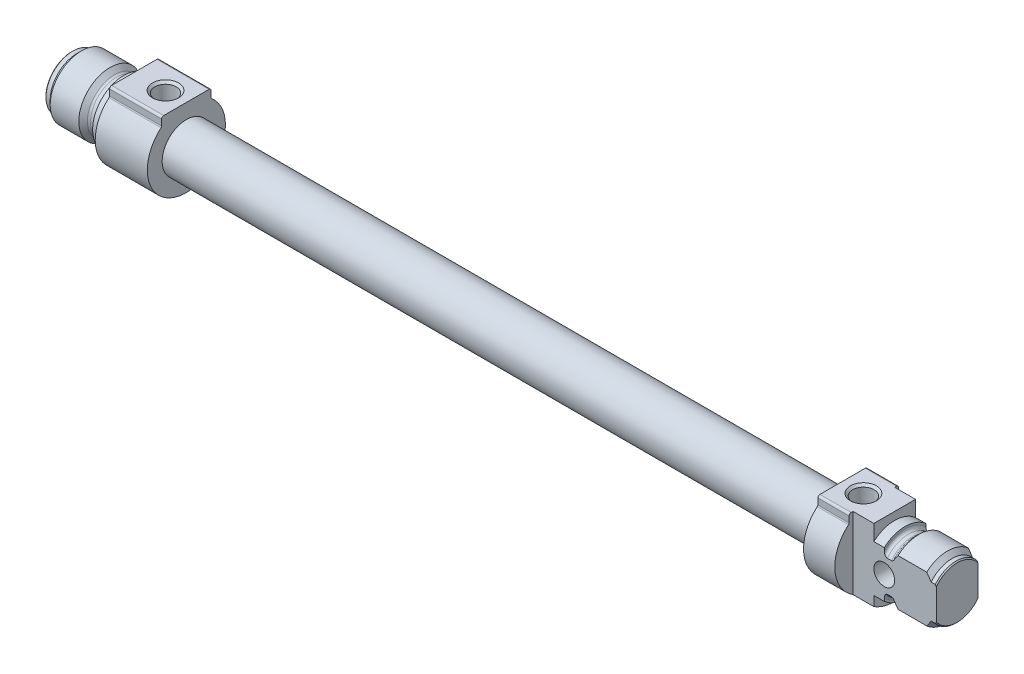
SolidWorks part; units mm, degrees
ref_plane "Ebene vorne" through (0, 0, 0) normal (0, 0, 1) x (1, 0, 0)
ref_plane "Ebene oben" through (0, 0, 0) normal (0, 1, 0) x (1, 0, 0)
ref_plane "Ebene rechts" through (0, 0, 0) normal (1, 0, 0) x (0, 0, -1)
sketch "Skizze1" plane through (0, 0, 0) normal (0, 0, 1) x (1, 0, 0)
  line L0 (0, 0) -> (0, 4.95)
  line L1 (0, 4.95) -> (0.2, 5.15)
  line L2 (0.2, 5.15) -> (1, 5.15)
  line L3 (1, 5.15) -> (1.85, 6)
  line L4 (1.85, 6) -> (7.35, 6)
  line L5 (7.35, 6) -> (8.1743, 5.1757)
  line L6 (8.5985, 5) -> (9.4, 5)
  line L7 (10, 5.6) -> (10, 6)
  line L8 (10, 6) -> (12, 6)
  line L9 (12, 6) -> (12, 0)
  line L10 (12, 0) -> (0, 0)
  line L11 (12, 0) -> (0, 0) construction
  arc A0 (8.1743, 5.1757) -> (8.5985, 5) centre (8.5985, 5.6) ccw
  arc A1 (9.4, 5) -> (10, 5.6) centre (9.4, 5.6) ccw
revolve "Rotation1" add sketch "Skizze1" angle 360 about L11 reverse direction yes
cosmetic thread "Gewindedarstellung1" parameters "D1"=6.267, "D2"=10.466
ref_plane "Ebene1" through (3, 0, 0) normal (1, 0, 0) x (0, 0, -1)
ref_plane "Ebene2" through (8, 0, 0) normal (1, 0, 0) x (0, 0, -1)
ref_plane "Ebene3" through (0, -8, 0) normal (0, 1, 0) x (1, 0, 0)
ref_plane "Ebene4" through (0, 0, 0) normal (0, 1, 0) x (1, 0, 0)
ref_plane "Ebene5" through (0, 0, 0) normal (0, 1, 0) x (1, 0, 0)
ref_plane "Ebene6" through (0, 0, 0) normal (0, 1, 0) x (1, 0, 0)
ref_plane "Ebene7" through (12, 0, 0) normal (1, 0, 0) x (0, 0, -1)
ref_plane "Ebene8" through (12, 0, 0) normal (1, 0, 0) x (0, 0, -1)
ref_plane "Ebene9" through (20, 0, 0) normal (1, 0, 0) x (0, 0, -1)
ref_plane "Ebene10" through (12, 0, 0) normal (1, 0, 0) x (0, 0, -1)
ref_plane "Ebene11" through (12, 0, 0) normal (1, 0, 0) x (0, 0, -1)
sketch "Skizze2" plane through (12, 0, 0) normal (1, 0, 0) x (0, 0, -1)
  line L0 (4.75, 5.9445) -> (4.75, 7.1)
  line L1 (4.35, 7.5) -> (-4.35, 7.5)
  line L2 (-4.75, 7.1) -> (-4.75, 5.9445)
  arc A0 (-4.8558, 5.7159) -> (4.8558, 5.7159) centre (0, 0) ccw
  arc A1 (4.8558, 5.7159) -> (4.75, 5.9445) centre (5.05, 5.9445) cw
  arc A2 (4.75, 7.1) -> (4.35, 7.5) centre (4.35, 7.1) ccw
  arc A3 (-4.35, 7.5) -> (-4.75, 7.1) centre (-4.35, 7.1) ccw
  arc A4 (-4.75, 5.9445) -> (-4.8558, 5.7159) centre (-5.05, 5.9445) cw
extrude "Aufsatz-Linear austragen1" add sketch "Skizze2" along normal blind 10
ref_plane "Ebene12" through (12, 0, 0) normal (1, 0, 0) x (0, 0, -1)
ref_plane "Ebene13" through (0, 0, 0) normal (0, 0, 1) x (1, 0, 0)
ref_plane "Ebene14" through (0, 0, 0) normal (0, 0, 1) x (1, 0, 0)
ref_plane "Ebene15" through (0, 0, 0) normal (0, 1, 0) x (1, 0, 0)
ref_plane "Ebene16" through (0, 0, 0) normal (0, 1, 0) x (1, 0, 0)
ref_plane "Ebene17" through (0, 0, -6.6) normal (0, 0, 1) x (1, 0, 0)
ref_plane "Ebene18" through (0, 0, 0) normal (0, 1, 0) x (1, 0, 0)
ref_plane "Ebene19" through (0, 0, 0) normal (0, 1, 0) x (1, 0, 0)
ref_plane "Ebene20" through (0, 1.1287, -0.199) normal (0, 0.9848, -0.1736) x (1, 0, 0)
ref_plane "Ebene21" through (0, -0.3485, 0.0615) normal (0, 0.9848, -0.1736) x (1, 0, 0)
sketch "Skizze3" plane through (0, 0, 0) normal (0, 0, 1) x (1, 0, 0)
  line L0 (22, 0) -> (22, 4.65)
  line L1 (22, 4.65) -> (148, 4.65)
  line L2 (148, 4.65) -> (148, 0)
  line L3 (148, 0) -> (22, 0)
  line L4 (148, 0) -> (22, 0) construction
revolve "Rotation2" add sketch "Skizze3" angle 360 about L4 reverse direction yes
ref_plane "Ebene22" through (148, 0, 0) normal (1, 0, 0) x (0, 0, -1)
sketch "Skizze4" plane through (148, 0, 0) normal (1, 0, 0) x (0, 0, -1)
  line L0 (4.75, 5.9445) -> (4.75, 7.1)
  line L1 (4.35, 7.5) -> (-4.35, 7.5)
  line L2 (-4.75, 7.1) -> (-4.75, 5.9445)
  arc A0 (-4.8558, 5.7159) -> (4.8558, 5.7159) centre (0, 0) ccw
  arc A1 (4.8558, 5.7159) -> (4.75, 5.9445) centre (5.05, 5.9445) cw
  arc A2 (4.75, 7.1) -> (4.35, 7.5) centre (4.35, 7.1) ccw
  arc A3 (-4.35, 7.5) -> (-4.75, 7.1) centre (-4.35, 7.1) ccw
  arc A4 (-4.75, 5.9445) -> (-4.8558, 5.7159) centre (-5.05, 5.9445) cw
extrude "Aufsatz-Linear austragen2" add sketch "Skizze4" along normal blind 10
ref_plane "Ebene23" through (148, 0, 0) normal (1, 0, 0) x (0, 0, -1)
ref_plane "Ebene24" through (158, 0, 0) normal (1, 0, 0) x (0, 0, -1)
ref_plane "Ebene25" through (0, 0, 6.6) normal (0, 0, 1) x (1, 0, 0)
ref_plane "Ebene26" through (0, 0, 0) normal (0, 1, 0) x (1, 0, 0)
ref_plane "Ebene27" through (0, 0, 0) normal (0, 1, 0) x (1, 0, 0)
ref_plane "Ebene28" through (0, 1.1287, 0.199) normal (0, 0.9848, 0.1736) x (1, 0, 0)
ref_plane "Ebene29" through (0, -0.3485, -0.0615) normal (0, 0.9848, 0.1736) x (1, 0, 0)
ref_plane "Ebene30" through (187, 0, 0) normal (1, 0, 0) x (0, 0, -1)
sketch "Skizze5" plane through (0, 0, 0) normal (0, 0, 1) x (1, 0, 0)
  line L0 (158, 0) -> (158, 6)
  line L1 (158, 6) -> (160, 6)
  line L2 (160, 6) -> (160, 5.6)
  line L3 (160.6, 5) -> (161.4015, 5)
  line L4 (161.8257, 5.1757) -> (162.65, 6)
  line L5 (162.65, 6) -> (168.15, 6)
  line L6 (168.15, 6) -> (169, 5.15)
  line L7 (169, 5.15) -> (169.8, 5.15)
  line L8 (169.8, 5.15) -> (170, 4.95)
  line L9 (170, 4.95) -> (170, 0)
  line L10 (170, 0) -> (158, 0)
  line L11 (170, 0) -> (158, 0) construction
  arc A0 (160, 5.6) -> (160.6, 5) centre (160.6, 5.6) ccw
  arc A1 (161.4015, 5) -> (161.8257, 5.1757) centre (161.4015, 5.6) ccw
revolve "Rotation3" add sketch "Skizze5" angle 360 about L11 reverse direction yes
cosmetic thread "Gewindedarstellung2" parameters "D1"=5.417, "D2"=10.466
ref_plane "Ebene31" through (179, 0, 0) normal (1, 0, 0) x (0, 0, -1)
ref_plane "Ebene32" through (187, 0, 0) normal (1, 0, 0) x (0, 0, -1)
ref_plane "Ebene33" through (187, 0, 0) normal (1, 0, 0) x (0, 0, -1)
sketch "Skizze6" plane through (0, 0, 0) normal (0, 1, 0) x (1, 0, 0)
  line L0 (154, 12) -> (154, 4)
  line L1 (154, 4) -> (170, 4)
  line L2 (170, 4) -> (170, -4)
  line L3 (170, -4) -> (154, -4)
  line L4 (154, -4) -> (154, -12)
  line L5 (154, -12) -> (178, -12)
  line L6 (178, -12) -> (178, 12)
  line L7 (178, 12) -> (154, 12)
extrude "Schnitt-Linear austragen1" cut sketch "Skizze6" along normal blind 7.5 and the other way blind 7.5
ref_plane "Ebene34" through (160, 0, 0) normal (1, 0, 0) x (0, 0, -1)
hole_wizard "Bohrung1" positions "Skizze8" profile "Skizze7" legacy
sketch "Skizze8" plane through (0, 0, -4) normal (0, 0, -1) x (-1, 0, 0)
  point P0 (-160, 0)
sketch "Skizze7" plane through (160, 0, -4) normal (1, 0, 0) x (0, 1, 0)
  line L0 (0, 0) -> (0, 8)
  line L1 (0, 8) -> (2, 8)
  line L2 (2, 8) -> (2, 0)
  line L3 (2, 0) -> (0, 0)
  line L4 (0, 110) -> (0, -10) construction
  dimension "Durchmesser" = 4
  dimension "Tiefe" = 8
hole_wizard "Bohrung2" positions "Skizze10" profile "Skizze9" legacy
sketch "Skizze10" plane through (0, 7.5, 0) normal (0, 1, 0) x (1, 0, 0)
  point P0 (18, 0)
sketch "Skizze9" plane through (18, 7.5, 0) normal (1, 0, 0) x (0, 0, 1)
  line L0 (0, 0) -> (0, 7.5)
  line L1 (0, 7.5) -> (2.067, 7.5)
  line L2 (2.067, 7.5) -> (2.067, 0.433)
  line L3 (2.067, 0.433) -> (2.5, 0)
  line L4 (2.5, 0) -> (0, 0)
  line L5 (0, -6.4453) -> (0, 115.525) construction
  line L6 (-2.067, 0.433) -> (-2.5, 0) construction
  dimension "Durchmesser" = 4.134
  dimension "Tiefe" = 7.5
  dimension "Senkwinkel1" = 90
  dimension "Senkdurchmesser3" = 5
cosmetic thread "Gewindedarstellung3" parameters "D1"=5.5, "D2"=5
hole_wizard "Bohrung3" positions "Skizze12" profile "Skizze11" legacy
sketch "Skizze12" plane through (0, 7.5, 0) normal (0, 1, 0) x (1, 0, 0)
  point P0 (152, 0)
sketch "Skizze11" plane through (152, 7.5, 0) normal (1, 0, 0) x (0, 0, 1)
  line L0 (0, 0) -> (0, 9.1934)
  line L1 (0, 9.1934) -> (2.067, 8)
  line L2 (2.067, 8) -> (2.067, 0.433)
  line L3 (2.067, 0.433) -> (2.5, 0)
  line L4 (2.5, 0) -> (0, 0)
  line L5 (0, -14.3089) -> (0, 102.4216) construction
  line L6 (0, 9.1934) -> (-2.067, 8) construction
  line L7 (-2.067, 0.433) -> (-2.5, 0) construction
  dimension "Durchmesser" = 4.134
  dimension "Tiefe" = 8
  dimension "Senkdurchmesser1" = 5
  dimension "Senkwinkel1" = 90
  dimension "Spitzenwinkel" = 120
cosmetic thread "Gewindedarstellung4" parameters "D1"=6, "D2"=5
sketch "Skizze13" plane through (0, 0, 0) normal (0, 0, 1) x (1, 0, 0)
  line L0 (-4, 0) -> (-4, 2)
  line L1 (-4, 2) -> (31.5, 2)
  line L2 (31.5, 2) -> (31.5, 4)
  line L3 (31.5, 4) -> (133.5, 4)
  line L4 (133.5, 4) -> (133.5, 0)
  line L5 (133.5, 0) -> (-4, 0)
  line L6 (133.5, 0) -> (-4, 0) construction
revolve "Schnitt-Rotation1" cut sketch "Skizze13" angle 360 about L6 reverse direction yes
ref_plane "Ebene35" through (-4, 0, 0) normal (1, 0, 0) x (0, 0, -1)
ref_plane "Ebene36" through (0, 7.5, 0) normal (0, 1, 0) x (1, 0, 0)
ref_plane "Ebene37" through (8, 0, 0) normal (1, 0, 0) x (0, 0, -1)
ref_plane "Ebene38" through (0, 0, 0) normal (1, 0, 0) x (0, 0, -1)
ref_plane "Ebene39" through (12, 0, 0) normal (1, 0, 0) x (0, 0, -1)
ref_plane "Ebene40" through (158, 0, 0) normal (1, 0, 0) x (0, 0, -1)
ref_plane "Ebene41" through (12, 0, 0) normal (1, 0, 0) x (0, 0, -1)
ref_plane "Ebene42" through (0, 7.5, 0) normal (0, 1, 0) x (1, 0, 0)
ref_plane "Ebene43" through (31.5, 0, 0) normal (1, 0, 0) x (0, 0, -1)
ref_plane "Ebene44" through (138.5, 0, 0) normal (1, 0, 0) x (0, 0, -1)
ref_plane "Ebene45" through (0, 0, 0) normal (0, 0, 1) x (1, 0, 0)
ref_plane "Ebene46" through (12, 0, 0) normal (1, 0, 0) x (0, 0, -1)
ref_plane "Ebene47" through (0, 7.5, 0) normal (0, 1, 0) x (1, 0, 0)
ref_plane "FDT_FRONT XY" through (12, 0, 0) normal (1, 0, 0) x (0, 0, -1)
ref_plane "FDT_FRONT XZ" through (0, 0, 0) normal (0, -1, 0) x (-1, 0, 0)
ref_plane "FDT_FRONT YZ" through (0, 0, 0) normal (0, 0, -1) x (-1, 0, 0)
ref_axis "FDT_FRONT X" through (12, 0, 80.9) along (0, 0, -1)
ref_axis "FDT_FRONT Y" through (12, -50, 0) along (0, 1, 0)
ref_axis "FDT_FRONT Z" through (80.9, 0, 0) along (-1, 0, 0)
sketch3d "FDT_FRONT"
  point P0 (12, 0, 0)
ref_plane "FDT_QSFRONT XY" through (0, 7.5, 0) normal (0, 1, 0) x (1, 0, 0)
ref_plane "FDT_QSFRONT XZ" through (18, 0, 0) normal (-1, 0, 0) x (0, 0, 1)
ref_plane "FDT_QSFRONT YZ" through (0, 0, 0) normal (0, 0, 1) x (1, 0, 0)
ref_axis "FDT_QSFRONT X" through (18, 7.5, -50) along (0, 0, 1)
ref_axis "FDT_QSFRONT Y" through (-80.9, 7.5, 0) along (1, 0, 0)
ref_axis "FDT_QSFRONT Z" through (18, 50, 0) along (0, -1, 0)
sketch3d "FDT_QSFRONT"
  point P0 (18, 7.5, 0)
ref_plane "FDT_QSREAR XY" through (0, 7.5, 0) normal (0, 1, 0) x (1, 0, 0)
ref_plane "FDT_QSREAR XZ" through (152, 0, 0) normal (-1, 0, 0) x (0, 0, 1)
ref_plane "FDT_QSREAR YZ" through (0, 0, 0) normal (0, 0, 1) x (1, 0, 0)
ref_axis "FDT_QSREAR X" through (152, 7.5, -50) along (0, 0, 1)
ref_axis "FDT_QSREAR Y" through (-80.9, 7.5, 0) along (1, 0, 0)
ref_axis "FDT_QSREAR Z" through (152, 50, 0) along (0, -1, 0)
sketch3d "FDT_QSREAR"
  point P0 (152, 7.5, 0)
ref_plane "FDT_REAR XY" through (158, 0, 0) normal (-1, 0, 0) x (0, 0, 1)
ref_plane "FDT_REAR XZ" through (0, 0, 0) normal (0, 1, 0) x (1, 0, 0)
ref_plane "FDT_REAR YZ" through (0, 0, 0) normal (0, 0, -1) x (-1, 0, 0)
ref_axis "FDT_REAR X" through (158, 0, 80.9) along (0, 0, -1)
ref_axis "FDT_REAR Y" through (158, 50, 0) along (0, -1, 0)
ref_axis "FDT_REAR Z" through (-80.9, 0, 0) along (1, 0, 0)
sketch3d "FDT_REAR"
  point P0 (158, 0, 0)
ref_plane "FDT_SMBR1 XY" through (31.5, 0, 0) normal (-1, 0, 0) x (0, 0, 1)
ref_plane "FDT_SMBR1 XZ" through (0, 0, 0) normal (0, -1, 0) x (-1, 0, 0)
ref_plane "FDT_SMBR1 YZ" through (0, 0, 0) normal (0, 0, 1) x (1, 0, 0)
ref_axis "FDT_SMBR1 X" through (31.5, 0, -80.9) along (0, 0, 1)
ref_axis "FDT_SMBR1 Y" through (31.5, -50, 0) along (0, 1, 0)
ref_axis "FDT_SMBR1 Z" through (-80.9, 0, 0) along (1, 0, 0)
sketch3d "FDT_SMBR1"
  point P0 (31.5, 0, 0)
ref_plane "FDT_SMBR2 XY" through (138.5, 0, 0) normal (-1, 0, 0) x (0, 0, 1)
ref_plane "FDT_SMBR2 XZ" through (0, 0, 0) normal (0, -1, 0) x (-1, 0, 0)
ref_plane "FDT_SMBR2 YZ" through (0, 0, 0) normal (0, 0, 1) x (1, 0, 0)
ref_axis "FDT_SMBR2 X" through (138.5, 0, -80.9) along (0, 0, 1)
ref_axis "FDT_SMBR2 Y" through (138.5, -50, 0) along (0, 1, 0)
ref_axis "FDT_SMBR2 Z" through (-80.9, 0, 0) along (1, 0, 0)
sketch3d "FDT_SMBR2"
  point P0 (138.5, 0, 0)
ref_plane "FDT_SWIVELAXIS XY" through (0, 0, 0) normal (0, 0, 1) x (1, 0, 0)
ref_plane "FDT_SWIVELAXIS XZ" through (0, 0, 0) normal (0, -1, 0) x (-1, 0, 0)
ref_plane "FDT_SWIVELAXIS YZ" through (160, 0, 0) normal (1, 0, 0) x (0, 0, -1)
ref_axis "FDT_SWIVELAXIS X" through (-80.9, 0, 0) along (1, 0, 0)
ref_axis "FDT_SWIVELAXIS Y" through (160, -50, 0) along (0, 1, 0)
ref_axis "FDT_SWIVELAXIS Z" through (160, 0, 80.9) along (0, 0, -1)
sketch3d "FDT_SWIVELAXIS"
  point P0 (160, 0, 0)
ref_plane "NUT XY" through (8, 0, 0) normal (1, 0, 0) x (0, 0, -1)
ref_plane "NUT XZ" through (0, 0, 0) normal (0, -1, 0) x (-1, 0, 0)
ref_plane "NUT YZ" through (0, 0, 0) normal (0, 0, -1) x (-1, 0, 0)
ref_axis "NUT X" through (8, 0, 80.9) along (0, 0, -1)
ref_axis "NUT Y" through (8, -50, 0) along (0, 1, 0)
ref_axis "NUT Z" through (80.9, 0, 0) along (-1, 0, 0)
sketch3d "NUT"
  point P0 (8, 0, 0)
ref_plane "ZR XY" through (0, 0, 0) normal (1, 0, 0) x (0, 0, -1)
ref_plane "ZR XZ" through (0, 0, 0) normal (0, -1, 0) x (-1, 0, 0)
ref_plane "ZR YZ" through (0, 0, 0) normal (0, 0, -1) x (-1, 0, 0)
ref_axis "ZR X" through (0, 0, 80.9) along (0, 0, -1)
ref_axis "ZR Y" through (0, -50, 0) along (0, 1, 0)
ref_axis "ZR Z" through (80.9, 0, 0) along (-1, 0, 0)
sketch3d "ZR"
  point P0 (0, 0, 0)
ref_plane "ZYL XY" through (12, 0, 0) normal (1, 0, 0) x (0, 0, -1)
ref_plane "ZYL XZ" through (0, 0, 0) normal (0, -1, 0) x (-1, 0, 0)
ref_plane "ZYL YZ" through (0, 0, 0) normal (0, 0, -1) x (-1, 0, 0)
ref_axis "ZYL X" through (12, 0, 80.9) along (0, 0, -1)
ref_axis "ZYL Y" through (12, -50, 0) along (0, 1, 0)
ref_axis "ZYL Z" through (80.9, 0, 0) along (-1, 0, 0)
sketch3d "ZYL"
  point P0 (12, 0, 0)
